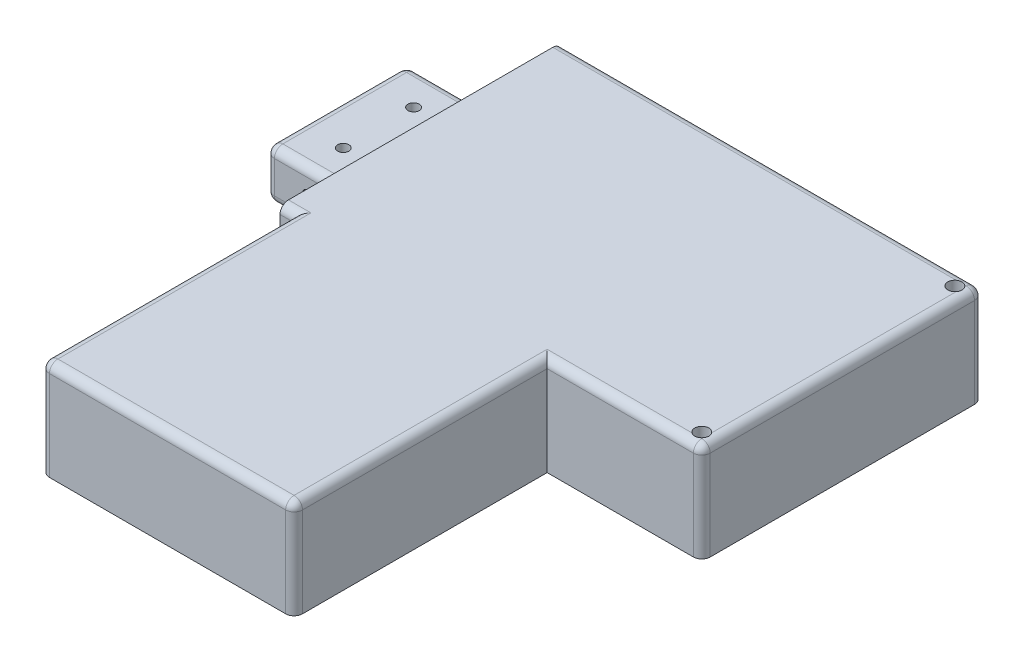
SolidWorks part; units mm, degrees
ref_plane "Front Plane" through (0, 0, 0) normal (0, 0, 1) x (1, 0, 0)
ref_plane "Top Plane" through (0, 0, 0) normal (0, 1, 0) x (1, 0, 0)
ref_plane "Right Plane" through (0, 0, 0) normal (1, 0, 0) x (0, 0, -1)
sketch "Sketch1" plane through (0, 0, 0) normal (0, 1, 0) x (1, 0, 0)
  line L0 (0, 0) -> (-39912.6941, 0) construction
  line L1 (0, 0) -> (0, -39912.6941) construction
  line L2 (-25, 0) -> (-25, -50000) construction
  line L3 (-75, 50) -> (75, 50)
  line L4 (-75, 50) -> (-75, -50)
  line L5 (-75, -50) -> (-70, -50)
  line L6 (75, 50) -> (75, -50)
  line L7 (-75, 50) -> (75, -50) construction
  line L8 (-75, -50) -> (75, 50) construction
  line L9 (20, -50) -> (75, -50)
  line L10 (-70, -140) -> (20, -140)
  line L11 (-70, -140) -> (-70, -50)
  line L13 (20, -140) -> (20, -50)
  line L14 (-70, -140) -> (20, -50) construction
  line L15 (-70, -50) -> (20, -140) construction
  point P5 (0, 0)
  point P12 (-25, -95)
  dimension "D1" = 150
  dimension "D2" = 100
  dimension "D3" = 100
  dimension "D4" = 90
  dimension "D5" = 90
extrude "Boss-Extrude1" add sketch "Sketch1" along normal blind 35
sketch "Sketch2" plane through (0, 35, 0) normal (0, 1, 0) x (1, 0, 0)
  line L0 (0, 0) -> (-50000, 0) construction
  line L1 (0, 0) -> (0, -50000) construction
  line L2 (-65, 40) -> (-65, -40) construction
  line L3 (-75, 50) -> (75, 50) construction
  line L4 (-75, 50) -> (-75, -50) construction
  line L5 (-75, -50) -> (75, -50) construction
  line L6 (75, 50) -> (75, -50) construction
  line L7 (-75, 50) -> (75, -50) construction
  line L8 (-75, -50) -> (75, 50) construction
  line L9 (-65, -40) -> (65, -40) construction
  line L10 (65, 40) -> (65, -40) construction
  line L11 (-65, 40) -> (65, 40) construction
  line L12 (65, 40) -> (75, 50) construction
  circle A0 centre (70, 45) radius 2.5
  circle A1 centre (70, -45) radius 2.5
  point P5 (0, 0)
  dimension "D2" = 5
  dimension "D1" = 10
extrude "Cut-Extrude1" cut sketch "Sketch2" against normal through all
sketch "Sketch3" plane through (0, 0, 0) normal (0, -1, 0) x (1, 0, 0)
  line L0 (0, 0) -> (-50000, 0) construction
  line L1 (0, 0) -> (0, -50000) construction
  line L2 (-25, 140) -> (-25, -49860) construction
  line L3 (-70, 140) -> (20, 140) construction
  line L4 (20, 50) -> (75, 50) construction
  circle A0 centre (-25, 0) radius 18.5
  circle A1 centre (-25, 115) radius 18.5
  point P9 (-25, 140)
  dimension "D1" = 37
  dimension "D2" = 37
  dimension "D3" = 65
extrude "Cut-Extrude2" cut sketch "Sketch3" against normal blind 7
sketch "Sketch4" plane through (0, 0, 0) normal (0, -1, 0) x (1, 0, 0)
  circle A0 centre (-25, 115) radius 14
  circle A1 centre (-25, 0) radius 14
  dimension "D1" = 28
  dimension "D2" = 28
extrude "Cut-Extrude3" cut sketch "Sketch4" against normal blind 25
sketch "Sketch5" plane through (-75, 0, 0) normal (-1, 0, 0) x (0, 0, 1)
  line L0 (0, 0) -> (0, -50000) construction
  line L1 (-50, 17.5) -> (49950, 17.5) construction
  line L2 (-50, 35) -> (-50, 0) construction
  line L4 (-25, 26.25) -> (25, 26.25)
  line L5 (-25, 26.25) -> (-25, 8.75)
  line L6 (-25, 8.75) -> (25, 8.75)
  line L7 (25, 26.25) -> (25, 8.75)
  line L8 (-25, 26.25) -> (25, 8.75) construction
  line L9 (-25, 8.75) -> (25, 26.25) construction
  point P7 (-50, 17.5)
  point P8 (0, 17.5)
  dimension "D1" = 17.5
  dimension "D2" = 50
extrude "Boss-Extrude2" add sketch "Sketch5" along normal blind 30 contours L4 L7 L6 L5
sketch "Sketch6" plane through (0, 26.25, 0) normal (0, 1, 0) x (1, 0, 0)
  line L0 (0, 0) -> (-50000, 0) construction
  line L1 (0, 0) -> (0, -50000) construction
  line L2 (-90, 25) -> (-90, -49975) construction
  line L3 (-105, 25) -> (-75, 25) construction
  circle A0 centre (-90, 12.5) radius 2
  circle A1 centre (-90, -12.5) radius 2
  point P9 (-90, 25)
  dimension "D1" = 4
  dimension "D2" = 12.5
extrude "Cut-Extrude4" cut sketch "Sketch6" against normal blind 8
sketch "Sketch7" plane through (0, 0, -25) normal (0, 0, -1) x (-1, 0, 0)
  line L0 (0, 0) -> (0, -50000) construction
  line L1 (95, 17.5) -> (-49905, 17.5) construction
  line L2 (105, 26.25) -> (105, 8.75) construction
  line L3 (90, 26.25) -> (90, -49973.75) construction
  line L4 (105, 26.25) -> (75, 26.25) construction
  circle A0 centre (90, 17.5) radius 2
  point P7 (105, 17.5)
  point P12 (90, 26.25)
  dimension "D1" = 4
extrude "Cut-Extrude5" cut sketch "Sketch7" against normal blind 8 contours A0
mirror "Mirror1" about plane through (0, 0, 0) normal (0, 0, 1) of "Cut-Extrude5"
fillet "Fillet1" radius 3 19 edges at (-70, 35, 95) (-72.5, 35, 50) (-25, 35, 140) (20, 35, 95) (47.5, 35, 50) (75, 17.5, 50) (75, 35, 0) (75, 17.5, -50) (0, 35, -50) (20, 17.5, 140) (-70, 17.5, 140) (-105, 17.5, -25) (-105, 8.75, 0) (-105, 17.5, 25) (-105, 26.25, 0) (-90, 8.75, 25) (-90, 26.25, 25) (-90, 8.75, -25) (-90, 26.25, -25)
